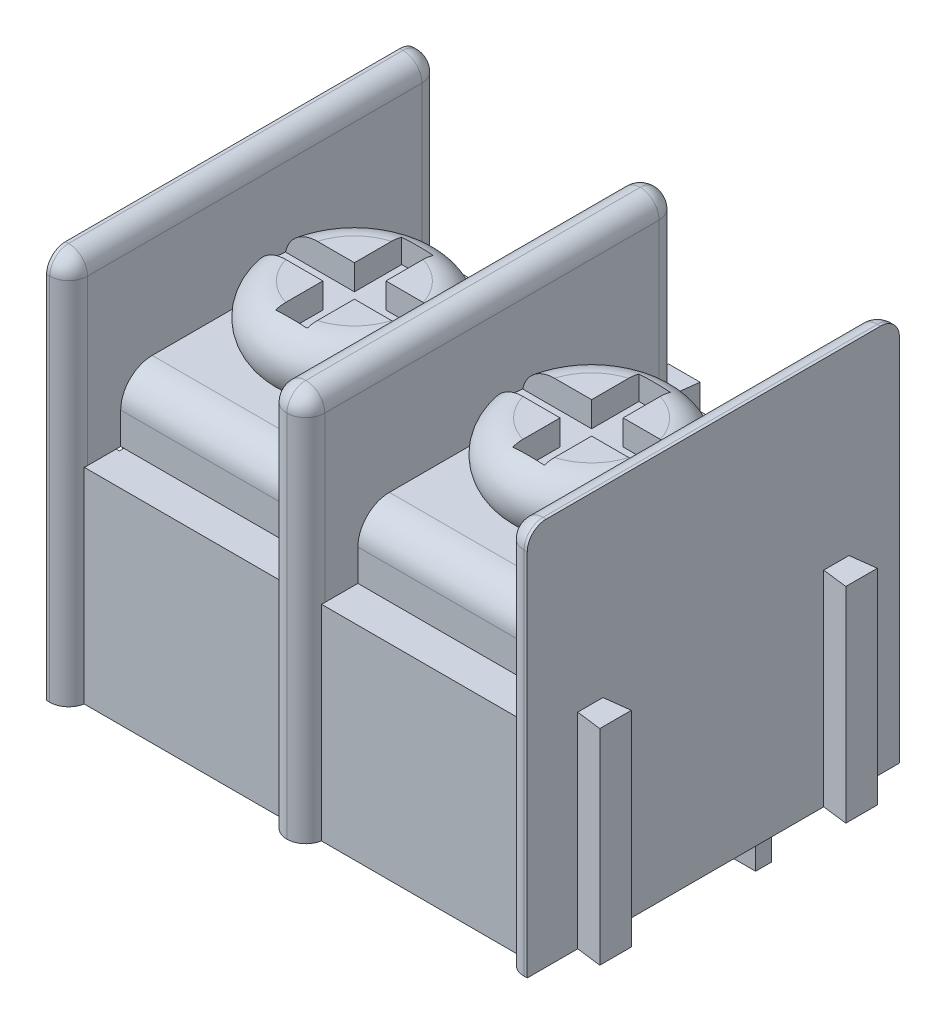
SolidWorks part; units mm, degrees
ref_plane "前视基准面" through (0, 0, 0) normal (0, 0, 1) x (1, 0, 0)
ref_plane "上视基准面" through (0, 0, 0) normal (0, 1, 0) x (1, 0, 0)
ref_plane "右视基准面" through (0, 0, 0) normal (1, 0, 0) x (0, 0, -1)
sketch "草图1" plane through (0, 0, 0) normal (0, 1, 0) x (1, 0, 0)
  line L0 (-11.1447, 0) -> (12.1543, 0) construction
  line L1 (-7.62, 5.9) -> (7.62, 5.9)
  line L2 (-7.62, 5.9) -> (-7.62, -5.9)
  line L3 (-7.62, -5.9) -> (7.62, -5.9)
  line L4 (7.62, 5.9) -> (7.62, -5.9)
  line L5 (0, 11.4931) -> (0, -8.9219) construction
  dimension "D1" = 15.24
  dimension "D2" = 11.8
extrude "拉伸1" add sketch "草图1" along normal blind 12.3
sketch "草图2" plane through (0, 12.3, 0) normal (0, 1, 0) x (-1, 0, 0)
  line L0 (0, 8.3959) -> (0, -7.6637) construction
  line L2 (-7.62, -5.9) -> (7.62, -5.9) construction
  line L3 (6.92, -5.9) -> (0.6, -5.9)
  line L4 (6.92, -5.9) -> (6.92, 5.9)
  line L5 (6.92, 5.9) -> (0.6, 5.9)
  line L7 (0.6, -5.9) -> (0.6, 5.9)
  line L8 (7.62, 5.9) -> (-7.62, 5.9) construction
  line L9 (7.62, -5.9) -> (7.62, 5.9) construction
  line L10 (-0.6, -5.9) -> (-0.6, 5.9)
  line L11 (-6.92, 5.9) -> (-0.6, 5.9)
  line L12 (-6.92, -5.9) -> (-6.92, 5.9)
  line L13 (-6.92, -5.9) -> (-0.6, -5.9)
  dimension "D1" = 0.6
  dimension "D2" = 0.7
extrude "切除-拉伸1" cut sketch "草图2" against normal blind 5.8
sketch "草图5" plane through (0, 6.5, 0) normal (0, 1, 0) x (1, 0, 0)
  line L0 (-0.6, -5.9) -> (-0.6, 5.9) construction
  line L1 (-6.92, -5.9) -> (-0.6, -5.9)
  line L2 (-6.92, -5.9) -> (-6.92, -5.4)
  line L3 (-6.92, -5.4) -> (-0.6, -5.4)
  line L4 (-0.6, -5.9) -> (-0.6, -5.4)
  line L5 (6.92, -5.9) -> (6.92, 5.9) construction
  line L6 (0.6, -5.9) -> (6.92, -5.9)
  line L7 (0.6, -5.9) -> (0.6, -5.4)
  line L8 (0.6, -5.4) -> (6.92, -5.4)
  line L9 (6.92, -5.9) -> (6.92, -5.4)
  dimension "D1" = 0.5
extrude "切除-拉伸2" cut sketch "草图5" against normal through all
fillet "圆角1" radius 0.6 16 edges at (6.92, 9.4, -5.9) (6.92, 12.3, 0) (6.92, 6.15, 5.9) (0.6, 9.4, -5.9) (-0.6, 9.4, -5.9) (-0.6, 12.3, 0) (-0.6, 6.15, 5.9) (0.6, 6.15, 5.9) (0.6, 12.3, 0) (-6.92, 9.4, -5.9) (-6.92, 12.3, 0) (-6.92, 6.15, 5.9) (-7.27, 12.3, -5.9) (-7.27, 12.3, 5.9) (7.27, 12.3, 5.9) (7.27, 12.3, -5.9)
sketch "草图6" plane through (0, 6.5, 0) normal (0, 1, 0) x (1, 0, 0)
  line L0 (6.92, -5.3) -> (6.92, 5.3) construction
  line L1 (6.92, -4.25) -> (0.6, -4.25)
  line L2 (6.92, -4.25) -> (6.92, 4.25)
  line L3 (6.92, 4.25) -> (0.6, 4.25)
  line L4 (0.6, -4.25) -> (0.6, 4.25)
  line L5 (0.6, 5.3) -> (0.6, -5.3) construction
  line L6 (0, 0) -> (-4.0708, 0) construction
  line L7 (0, 0) -> (0, -8.8479) construction
  dimension "D1" = 8.5
extrude "凸台-拉伸1" add sketch "草图6" along normal blind 2
sketch "草图7" plane through (0, 0, 0) normal (0, 0, 1) x (1, 0, 0)
  line L0 (3.76, 8.5) -> (3.76, 10.5)
  line L1 (6.92, 8.5) -> (0.6, 8.5) construction
  line L2 (3.76, 10.5) -> (2.01, 10.5)
  line L4 (2.01, 8.5) -> (3.76, 8.5)
  arc A0 (2.01, 10.5) -> (2.01, 8.5) centre (2.01, 9.5) ccw
  dimension "D1" = 2.75
  dimension "D2" = 2
revolve "旋转1" add sketch "草图7" angle 360 about L0
sketch "草图8" plane through (0, 10.5, 0) normal (0, 1, 0) x (1, 0, 0)
  line L0 (3.76, -2) -> (3.76, 2) construction
  line L1 (6.76, 0) -> (0.76, 0) construction
  line L2 (3.76, -12.0394) -> (3.76, 2) construction
  line L3 (6.76, 0.5) -> (4.26, 0.5)
  line L4 (4.26, -2) -> (4.26, -0.5)
  line L5 (6.76, -0.5) -> (4.26, -0.5)
  line L6 (3.26, -2) -> (3.26, -0.5)
  line L7 (6.76, -0.5) -> (6.76, 0.5)
  line L8 (0.76, -0.5) -> (0.76, 0.5)
  line L11 (6.76, 0) -> (0.76, 0) construction
  line L12 (4.26, -2) -> (3.26, -2)
  line L13 (4.26, 2) -> (3.26, 2)
  line L14 (3.26, -12.0394) -> (3.26, 2) construction
  line L15 (4.26, -12.0394) -> (4.26, 2) construction
  line L16 (3.26, -0.5) -> (0.76, -0.5)
  line L17 (6.76, -0.5) -> (0.76, -0.5) construction
  line L18 (4.26, 0.5) -> (4.26, 2)
  line L19 (3.26, 0.5) -> (3.26, 2)
  line L20 (3.26, 0.5) -> (0.76, 0.5)
  line L21 (6.76, 0.5) -> (0.76, 0.5) construction
  circle A1 centre (3.76, 0) radius 1.75 construction
  point P3 (3.76, 0)
  point P6 (3.76, 0)
  dimension "D1" = 4
  dimension "D2" = 6
  dimension "D3" = 0.5
  dimension "D4" = 0.5
extrude "切除-拉伸3" cut sketch "草图8" against normal blind 0.8
fillet "圆角2" radius 1 2 edges at (3.76, 8.5, 4.25) (3.76, 8.5, -4.25)
sketch "草图3" plane through (0, 0, 0) normal (0, -1, 0) x (1, 0, 0)
  line L0 (9.9133, -4.9) -> (-9.4768, -4.9) construction
  line L1 (0, -8.128) -> (0, 7.9902) construction
  line L2 (3.31, -5.15) -> (4.31, -4.65) construction
  line L3 (-3.31, -4.65) -> (-4.31, -4.65)
  line L4 (-3.31, -4.65) -> (-3.31, -5.15)
  line L5 (-3.31, -5.15) -> (-4.31, -5.15)
  line L6 (-4.31, -4.65) -> (-4.31, -5.15)
  line L7 (-3.31, -4.65) -> (-4.31, -5.15) construction
  line L8 (-3.31, -5.15) -> (-4.31, -4.65) construction
  line L9 (3.31, -4.65) -> (4.31, -5.15) construction
  line L10 (4.31, -4.65) -> (4.31, -5.15)
  line L11 (3.31, -5.15) -> (4.31, -5.15)
  line L12 (3.31, -4.65) -> (3.31, -5.15)
  line L13 (3.31, -4.65) -> (4.31, -4.65)
  line L14 (7.62, -5.9) -> (-7.62, -5.9) construction
  point P8 (-3.81, -4.9)
  point P15 (3.81, -4.9)
  dimension "D1" = 1
  dimension "D4" = 3.81
  dimension "D5" = 1
  dimension "D6" = 0.5
extrude "拉伸2" add sketch "草图3" along normal blind 4
mirror "镜向1" about plane through (0, 0, 0) normal (1, 0, 0) of "圆角2", "切除-拉伸3", "旋转1", "凸台-拉伸1"
sketch "草图9" plane through (0, 0, 0) normal (0, 1, 0) x (1, 0, 0)
  line L0 (0.4, 5.9) -> (0.5, 6.7)
  line L1 (7.62, 5.9) -> (-7.62, 5.9) construction
  line L2 (0.5, 6.7) -> (-0.5, 6.7)
  line L3 (-0.5, 6.7) -> (-0.4, 5.9)
  line L4 (-0.4, 5.9) -> (0.4, 5.9)
  line L5 (5.3986, 0) -> (-5.3986, 0) construction
  line L6 (0, -4.7271) -> (0, 4.7271) construction
  line L7 (8.42, 4.4) -> (8.42, 3.4)
  line L8 (8.42, 3.4) -> (7.62, 3.5)
  line L9 (7.62, -5.9) -> (7.62, 5.9) construction
  line L10 (7.62, 3.5) -> (7.62, 4.3)
  line L11 (7.62, 4.3) -> (8.42, 4.4)
  line L12 (7.62, -4.3) -> (8.42, -4.4)
  line L13 (7.62, -3.5) -> (7.62, -4.3)
  line L14 (8.42, -3.4) -> (7.62, -3.5)
  line L15 (8.42, -4.4) -> (8.42, -3.4)
  line L16 (-6.82, 4.4) -> (-6.82, 3.4)
  line L17 (-6.82, 3.4) -> (-7.62, 3.5)
  line L18 (-7.62, 3.5) -> (-7.62, 4.3)
  line L19 (-7.62, 4.3) -> (-6.82, 4.4)
  line L20 (-7.62, -4.3) -> (-6.82, -4.4)
  line L21 (-7.62, -3.5) -> (-7.62, -4.3)
  line L22 (-6.82, -3.4) -> (-7.62, -3.5)
  line L23 (-6.82, -4.4) -> (-6.82, -3.4)
  line L24 (-7.62, 5.9) -> (-7.62, -5.9) construction
  point P10 (0, 0)
  point P13 (0, 0)
  dimension "D1" = 1
  dimension "D2" = 0.8
  dimension "D3" = 0.8
  dimension "D4" = 1.5
extrude "凸台-拉伸2" add sketch "草图9" along normal up to surface (6.5 mm away) contours L3 L4 L0 L2 | L7 L8 L10 L11 | L13 L12 L15 L14 region at (0, 0, -6.3148) up to face at (3.76, 6.5, -5.1914)
extrude "切除-拉伸4" cut sketch "草图9<3>" along normal up to surface (6.5 mm away) contours L19 L18 L17 L16 | L20 L23 L22 L21 region at (-7.2052, 0, -3.9) region at (-7.2052, 0, 3.9) up to face at (3.76, 6.5, 4.9834)
sketch "草图9<3>" plane through (0, 0, 0) normal (0, 1, 0) x (1, 0, 0) same geometry as "草图9"
